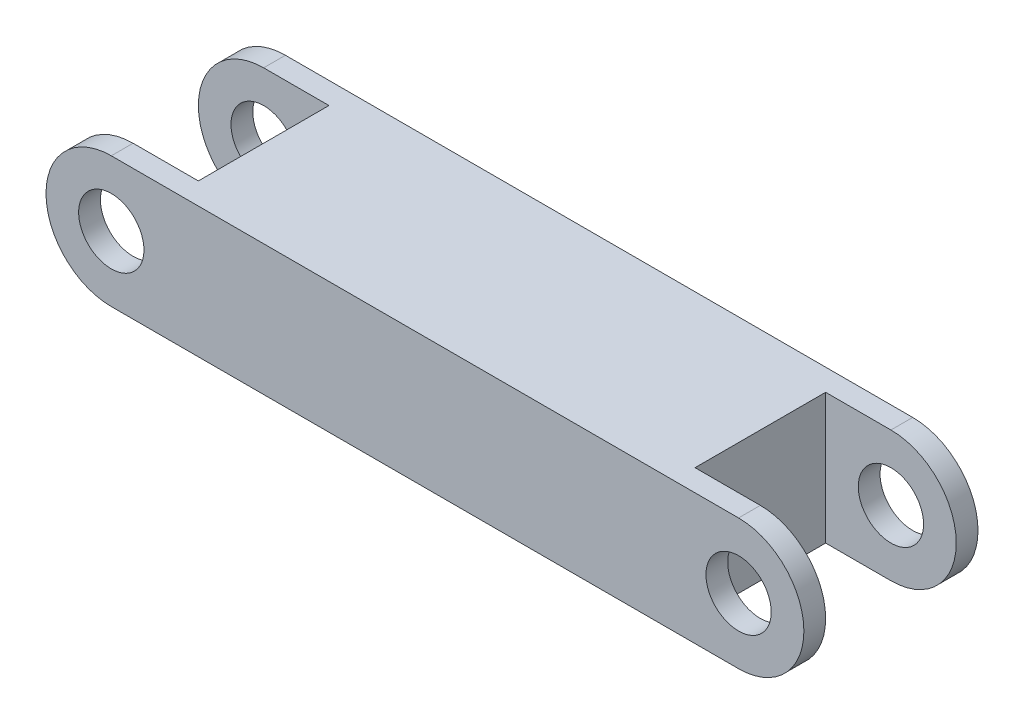
SolidWorks part; units mm, degrees
ref_plane "Front Plane" through (0, 0, 0) normal (0, 0, 1) x (1, 0, 0)
ref_plane "Top Plane" through (0, 0, 0) normal (0, 1, 0) x (1, 0, 0)
ref_plane "Right Plane" through (0, 0, 0) normal (1, 0, 0) x (0, 0, -1)
sketch "Sketch1" plane through (0, 0, 0) normal (0, 0, 1) x (1, 0, 0)
  line L0 (0, 0) -> (144.095, 0) construction
  line L1 (0, 15) -> (144.095, 15)
  line L2 (0, -15) -> (144.095, -15)
  arc A0 (0, 15) -> (0, -15) centre (0, 0) ccw
  arc A1 (144.095, -15) -> (144.095, 15) centre (144.095, 0) ccw
  circle A2 centre (0, 0) radius 7.5
  circle A3 centre (144.095, 0) radius 7.5
  point P3 (72.0475, 0)
  point P12 (144.095, 0)
  dimension "D1" = 15
  dimension "D2" = 15
  dimension "D3" = 30
extrude "Boss-Extrude1" add sketch "Sketch1" along normal blind 40
sketch "Sketch2" plane through (0, 15, 0) normal (0, 1, 0) x (1, 0, 0)
  line L0 (-15, 0) -> (-15, -40) construction
  line L1 (15, -5) -> (-15, -5)
  line L2 (15, -5) -> (15, -35)
  line L3 (15, -35) -> (-15, -35)
  line L4 (-15, -5) -> (-15, -35)
  line L5 (159.095, -40) -> (159.095, 0) construction
  line L6 (0, -40) -> (0, 0) construction
  line L15 (129.095, -35) -> (159.095, -35)
  line L16 (129.095, -35) -> (129.095, -5)
  line L17 (129.095, -5) -> (159.095, -5)
  line L18 (159.095, -35) -> (159.095, -5)
  line L19 (144.095, -40) -> (144.095, 0) construction
  point P7 (-15, -20)
  point P10 (0, -20)
  point P15 (159.095, -20)
  point P19 (144.095, -20)
  dimension "D1" = 30
  dimension "D2" = 30
  dimension "D3" = 30
  dimension "D4" = 30
extrude "Cut-Extrude1" cut sketch "Sketch2" against normal through all
